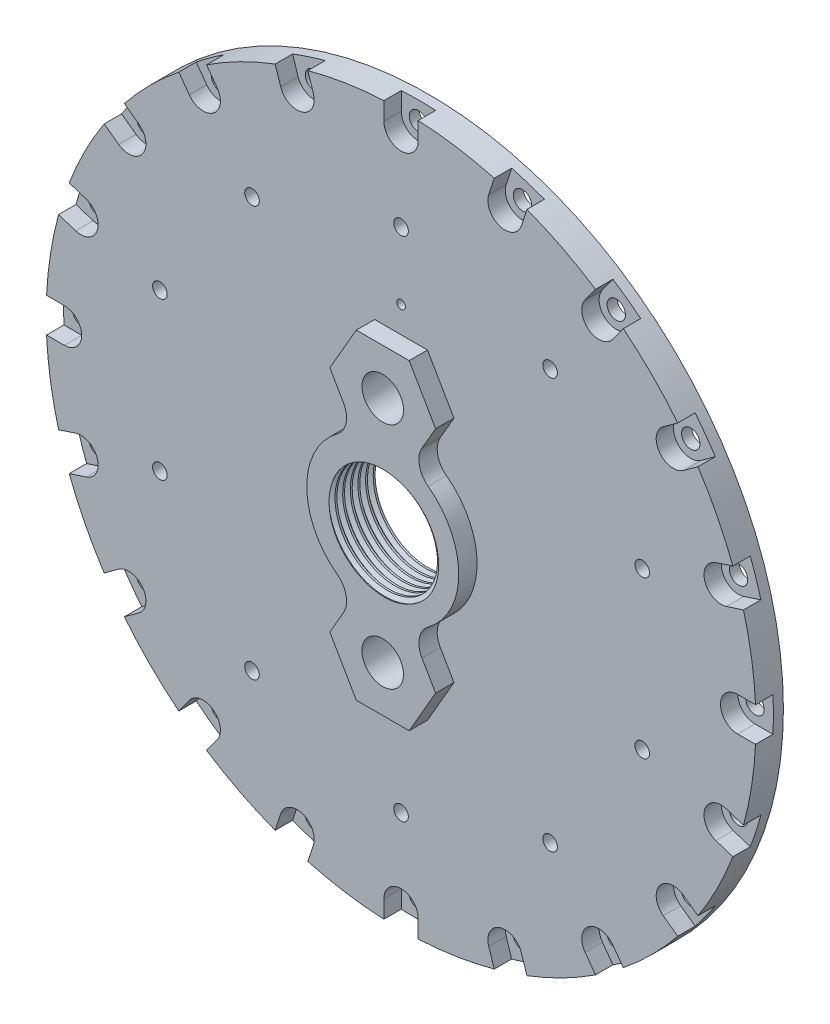
SolidWorks part; units mm, degrees
material "AISI 316 Stainless Steel Sheet (SS)"
ref_plane "Front Plane" through (0, 0, 0) normal (0, 0, 1) x (1, 0, 0)
ref_plane "Top Plane" through (0, 0, 0) normal (0, 1, 0) x (1, 0, 0)
ref_plane "Right Plane" through (0, 0, 0) normal (1, 0, 0) x (0, 0, -1)
sketch "Sketch1" plane through (0, 0, 0) normal (1, 0, 0) x (0, 0, -1)
  line L0 (0, 21.082) -> (0, 98.425)
  line L1 (0, 98.425) -> (7.62, 98.425)
  line L2 (7.62, 98.425) -> (7.62, 88.6333)
  line L3 (7.62, 83.82) -> (5.08, 83.82)
  line L4 (5.08, 83.82) -> (5.08, 56.8325)
  line L5 (5.08, 56.8325) -> (7.62, 56.8325)
  line L6 (7.62, 56.8325) -> (7.62, 53.0225)
  line L7 (7.62, 14.732) -> (-5.08, 14.732)
  line L8 (-5.08, 14.732) -> (-5.08, 21.082)
  line L9 (-5.08, 21.082) -> (0, 21.082)
  line L10 (0, 0) -> (59.2702, 0) construction
  line L12 (7.62, 49.6951) -> (6.2992, 49.6951)
  line L14 (7.62, 47.0535) -> (6.2992, 47.0535)
  line L15 (6.2992, 49.6951) -> (6.2992, 47.0535)
  line L20 (7.62, 47.0535) -> (7.62, 46.0375)
  line L21 (7.62, 85.1027) -> (7.62, 83.82)
  line L22 (7.62, 50.4825) -> (7.62, 49.6951)
  line L23 (7.62, 21.59) -> (7.62, 14.732)
  line L24 (7.62, 46.0375) -> (5.08, 46.0375)
  line L26 (7.62, 21.59) -> (5.08, 21.59)
  line L27 (5.08, 46.0375) -> (5.08, 21.59)
  line L28 (7.62, 53.0225) -> (6.35, 53.0225)
  line L32 (7.62, 50.4825) -> (6.35, 50.4825)
  line L33 (6.35, 53.0225) -> (6.35, 50.4825)
  line L35 (7.62, 88.6333) -> (5.6642, 88.6333)
  line L37 (7.62, 85.1027) -> (5.6642, 85.1027)
  line L38 (5.6642, 88.6333) -> (5.6642, 85.1027)
  point P19 (6.35, 51.7525)
  point P22 (6.2992, 48.3743)
  point P31 (5.6642, 86.868)
  dimension "D1" = 196.85
  dimension "D2" = 2.54
  dimension "D3" = 7.62
  dimension "D4" = 2.54
  dimension "D5" = 113.665
  dimension "D6" = 12.7
  dimension "D7" = 29.464
  dimension "D8" = 6.35
  dimension "D9" = 2.6416
  dimension "D10" = 96.7486
  dimension "D11" = 1.3208
  dimension "D12" = 167.64
  dimension "D13" = 92.075
  dimension "D14" = 43.18
  dimension "D15" = 1.27
  dimension "D16" = 2.54
  dimension "D17" = 103.505
  dimension "D18" = 1.9558
  dimension "D19" = 3.5306
  dimension "D20" = 173.736
revolve "Revolve1" add sketch "Sketch1" angle 360 about L10 region at (0, 54.7882, -2.7116)
thread "Thread1" pitch 2.1167 method cut profile "Thread Profile1" start angle 0, offset 4.318, length 0, pitch 2.1167, diameter 29.464
ref_plane "Plane1" through (-14.732, 0, 9.398) normal (0, -1, 0) x (-1, 0, 0)
sketch "Thread Profile1" plane through (-14.732, 0, 9.398) normal (0, -1, 0) x (-1, 0, 0)
  line L0 (0, 0) -> (0, 2.1167) construction
  line L1 (0, 0) -> (1.1457, 0.6615)
  line L2 (1.1457, 0.6615) -> (1.1457, 0.926)
  line L3 (1.1457, 0.926) -> (0, 1.5875)
  line L4 (1.1457, 0.7937) -> (0, 0.7937) construction
  line L11 (0, 0) -> (0, 1.5875)
  point P2 (0, 0)
  dimension "Pitch" = 2.1167
  dimension "Profile_Angle" = 60
  dimension "Profile_Land" = 0.2646
  dimension "Profile_Height" = 1.1457
sketch "Sketch15" plane through (0, 0, 0) normal (0, 0, 1) x (1, 0, 0)
  line L10 (0, 0) -> (104.8126, 0) construction
  line L11 (7.3323, 19.05) -> (14.6647, 31.75)
  line L12 (14.6647, 31.75) -> (7.3323, 44.45)
  line L13 (7.3323, 44.45) -> (-7.3323, 44.45)
  line L14 (-7.3323, 44.45) -> (-14.6647, 31.75)
  line L15 (-14.6647, 31.75) -> (-7.3323, 19.05)
  line L16 (-7.3323, 19.05) -> (7.3323, 19.05)
  line L17 (-7.3323, -19.05) -> (7.3323, -19.05)
  line L18 (-14.6647, -31.75) -> (-7.3323, -19.05)
  line L19 (-7.3323, -44.45) -> (-14.6647, -31.75)
  line L20 (7.3323, -44.45) -> (-7.3323, -44.45)
  line L21 (14.6647, -31.75) -> (7.3323, -44.45)
  line L22 (7.3323, -19.05) -> (14.6647, -31.75)
  circle A8 centre (0, 31.75) radius 12.7 construction
  circle A9 centre (0, -31.75) radius 12.7 construction
  dimension "D2" = 63.5
  dimension "D1" = 25.4
extrude "Boss-Extrude1" add sketch "Sketch15" along normal up to surface (5.08 mm away) up to face at (21.082, 0, 5.08)
hole_wizard "1/2-20 Tapped Hole2" positions "Sketch20" profile "Sketch17" tap size "1/2-20" standard "ANSI Inch" end condition through all
sketch "Sketch20" plane through (0, 0, 5.08) normal (0, 0, 1) x (1, 0, 0)
  point P9 (0, 31.75)
  point P16 (0, -31.75)
sketch "Sketch17" plane through (0, 31.75, 5.08) normal (1, 0, 0) x (0, -1, 0)
  line L0 (0, 0) -> (0, 13.4424)
  line L1 (0, 13.4424) -> (5.7544, 13.4424)
  line L2 (5.7544, 13.4424) -> (5.7544, 0)
  line L5 (5.7544, 0) -> (0, 0)
  line L11 (0, -6.35) -> (0, 107.95) construction
  dimension "Thru Tap Drill Dia." = 11.5087
  dimension "Thru Tap Drill Depth" = 13.4424
cosmetic thread "Hole Thread3" parameters "D2"=12.7
cosmetic thread "Hole Thread4" parameters "D2"=12.7
hole_wizard "CBORE for #10 Socket Head Cap Screw1" positions "Sketch28" profile "Sketch9" counterbore size "#10" standard "ANSI Inch" end condition up to next
sketch "Sketch28" plane through (0, 0, 0) normal (0, 0, 1) x (1, 0, 0)
  circle A0 centre (0, 0) radius 93.345 construction
  point P0 (0, 93.345)
  point P16 (28.8452, 88.7764)
  point P17 (54.8668, 75.5177)
  point P18 (75.5177, 54.8668)
  point P19 (88.7764, 28.8452)
  point P20 (93.345, 0)
  point P21 (88.7764, -28.8452)
  point P22 (75.5177, -54.8668)
  point P23 (54.8668, -75.5177)
  point P24 (28.8452, -88.7764)
  point P25 (0, -93.345)
  point P26 (-28.8452, -88.7764)
  point P27 (-54.8668, -75.5177)
  point P28 (-75.5177, -54.8668)
  point P29 (-88.7764, -28.8452)
  point P30 (-93.345, 0)
  point P31 (-88.7764, 28.8452)
  point P32 (-75.5177, 54.8668)
  point P33 (-54.8668, 75.5177)
  point P34 (-28.8452, 88.7764)
  dimension "D1" = 186.69
  dimension "D2" = 20
sketch "Sketch9" plane through (0, 93.345, 0) normal (1, 0, 0) x (0, -1, 0)
  line L0 (0, 0) -> (0, 7.62)
  line L1 (0, 7.62) -> (2.5527, 7.62)
  line L3 (2.5527, 7.62) -> (2.5527, 4.826)
  line L4 (2.5527, 4.826) -> (4.7625, 4.826)
  line L5 (4.7625, 4.826) -> (4.7625, 0)
  line L7 (4.7625, 0) -> (0, 0)
  line L11 (0, -6.35) -> (0, 107.95) construction
  dimension "Thru Hole Dia." = 5.1054
  dimension "Thru Hole Depth" = 7.62
  dimension "C'Bore Dia." = 9.525
  dimension "C'Bore Depth" = 4.826
sketch "Sketch29" plane through (0, 0, 0) normal (0, 0, 1) x (1, 0, 0)
  line L0 (4.7625, 93.345) -> (4.7625, 98.3097)
  line L1 (-4.7625, 93.345) -> (-4.7625, 98.3097)
  line L2 (33.3746, 87.3047) -> (34.9088, 92.0264)
  line L3 (24.3158, 90.2481) -> (25.85, 94.9698)
  line L4 (58.7198, 72.7184) -> (61.6379, 76.7349)
  line L5 (51.0139, 78.317) -> (53.9321, 82.3336)
  line L6 (78.317, 51.0139) -> (82.3336, 53.9321)
  line L7 (72.7184, 58.7198) -> (76.7349, 61.6379)
  line L8 (90.2481, 24.3158) -> (94.9698, 25.85)
  line L9 (87.3047, 33.3746) -> (92.0264, 34.9088)
  line L10 (93.345, -4.7625) -> (98.3097, -4.7625)
  line L11 (93.345, 4.7625) -> (98.3097, 4.7625)
  line L12 (87.3047, -33.3746) -> (92.0264, -34.9088)
  line L13 (90.2481, -24.3158) -> (94.9698, -25.85)
  line L14 (72.7184, -58.7198) -> (76.7349, -61.6379)
  line L15 (78.317, -51.0139) -> (82.3336, -53.9321)
  line L16 (51.0139, -78.317) -> (53.9321, -82.3336)
  line L17 (58.7198, -72.7184) -> (61.6379, -76.7349)
  line L18 (24.3158, -90.2481) -> (25.85, -94.9698)
  line L19 (33.3746, -87.3047) -> (34.9088, -92.0264)
  line L20 (-4.7625, -93.345) -> (-4.7625, -98.3097)
  line L21 (4.7625, -93.345) -> (4.7625, -98.3097)
  line L22 (-33.3746, -87.3047) -> (-34.9088, -92.0264)
  line L23 (-24.3158, -90.2481) -> (-25.85, -94.9698)
  line L24 (-58.7198, -72.7184) -> (-61.6379, -76.7349)
  line L25 (-51.0139, -78.317) -> (-53.9321, -82.3336)
  line L26 (-78.317, -51.0139) -> (-82.3336, -53.9321)
  line L27 (-72.7184, -58.7198) -> (-76.7349, -61.6379)
  line L28 (-90.2481, -24.3158) -> (-94.9698, -25.85)
  line L29 (-87.3047, -33.3746) -> (-92.0264, -34.9088)
  line L30 (-93.345, 4.7625) -> (-98.3097, 4.7625)
  line L31 (-93.345, -4.7625) -> (-98.3097, -4.7625)
  line L32 (-87.3047, 33.3746) -> (-92.0264, 34.9088)
  line L33 (-90.2481, 24.3158) -> (-94.9698, 25.85)
  line L34 (-72.7184, 58.7198) -> (-76.7349, 61.6379)
  line L35 (-78.317, 51.0139) -> (-82.3336, 53.9321)
  line L36 (-51.0139, 78.317) -> (-53.9321, 82.3336)
  line L37 (-58.7198, 72.7184) -> (-61.6379, 76.7349)
  line L38 (-24.3158, 90.2481) -> (-25.85, 94.9698)
  line L39 (-33.3746, 87.3047) -> (-34.9088, 92.0264)
  circle A0 centre (0, 93.345) radius 4.7625 construction
  circle A1 centre (0, 0) radius 98.425 construction
  circle A2 centre (28.8452, 88.7764) radius 4.7625
  circle A3 centre (0, 93.345) radius 4.7625
  circle A4 centre (54.8668, 75.5177) radius 4.7625
  circle A5 centre (0, 0) radius 98.425
  circle A6 centre (0, 0) radius 98.425
  circle A7 centre (75.5177, 54.8668) radius 4.7625
  circle A8 centre (88.7764, 28.8452) radius 4.7625
  circle A9 centre (93.345, 0) radius 4.7625
  circle A10 centre (88.7764, -28.8452) radius 4.7625
  circle A11 centre (75.5177, -54.8668) radius 4.7625
  circle A12 centre (54.8668, -75.5177) radius 4.7625
  circle A13 centre (28.8452, -88.7764) radius 4.7625
  circle A14 centre (0, -93.345) radius 4.7625
  circle A15 centre (-28.8452, -88.7764) radius 4.7625
  circle A16 centre (-54.8668, -75.5177) radius 4.7625
  circle A17 centre (-75.5177, -54.8668) radius 4.7625
  circle A18 centre (-88.7764, -28.8452) radius 4.7625
  circle A19 centre (-93.345, 0) radius 4.7625
  circle A20 centre (-88.7764, 28.8452) radius 4.7625
  circle A21 centre (-75.5177, 54.8668) radius 4.7625
  circle A22 centre (-54.8668, 75.5177) radius 4.7625
  circle A23 centre (-28.8452, 88.7764) radius 4.7625
  circle A25 centre (28.8452, 88.7764) radius 2.5527 construction
  point P2 (0, 0)
  point P129 (0, 0)
  circle M62 centre (0, 93.345) radius 4.7625
  circle M82 centre (0, 0) radius 98.425
  dimension "D1" = 0
  dimension "D2" = 20
extrude "Cut-Extrude1" cut sketch "Sketch29" against normal up to surface (4.826 mm away) contours L1 L0 M62 M82 region at (0, 98.2155, 0) up to face at (2.5527, 93.345, -4.826)
pattern_circular "CirPattern2" count 20 over 360 about axis through (0, 0, 0) along (0, 0, 1) of "Cut-Extrude1"
fillet "Fillet1" radius 6.35 4 edges at (-7.6711, 19.6368, 2.54) (-7.6711, -19.6368, 2.54) (7.6711, -19.6368, 2.54) (7.6711, 19.6368, 2.54)
hole_wizard "3/32 (0.09375) Dowel Hole1" positions "Sketch23" profile "Sketch22" hole size "3/32" standard "ANSI Inch" end condition up to next
sketch "Sketch23" plane through (0, 0, -6.35) normal (0, 0, -1) x (-1, 0, 0)
  line L0 (0, 50.4825) -> (0, 53.0225) construction
  circle A1 centre (0, 0) radius 50.4825 construction
  circle A2 centre (0, 0) radius 53.0225 construction
  point P0 (0, 51.7525)
  point P15 (0, 51.7525)
sketch "Sketch22" plane through (0, 51.7525, -6.35) normal (1, 0, 0) x (0, 1, 0)
  line L0 (0, 0) -> (0, 6.35)
  line L1 (0, 6.35) -> (1.1906, 6.35)
  line L2 (1.1906, 6.35) -> (1.1906, 0)
  line L5 (1.1906, 0) -> (0, 0)
  line L11 (0, -6.35) -> (0, 107.95) construction
  dimension "Thru Hole Dia." = 2.3812
  dimension "Thru Hole Depth" = 6.35
sketch "Sketch24" plane through (0, 0, 0) normal (0, 0, 1) x (1, 0, 0)
  line L0 (0, 56.8325) -> (0, 83.82) construction
  line L2 (14.6024, 92.1958) -> (0, 0) construction
  circle A0 centre (0, 0) radius 70.3263 construction
  circle A1 centre (0, 0) radius 56.8325 construction
  circle A2 centre (0, 0) radius 56.8325 construction
  circle A3 centre (0, 0) radius 83.82 construction
  arc A4 (0, 93.345) -> (28.8452, 88.7764) centre (0, 0) cw construction
  arc A6 (24.3158, 90.2481) -> (33.3746, 87.3047) centre (28.8452, 88.7764) ccw construction
  point P0 (0, 70.3263)
  point P14 (0, 70.3263)
  point P17 (0, 0)
sketch "Sketch25" plane through (0, 0, 0) normal (0, 0, 1) x (1, 0, 0)
  point P0 (0, 70.3263)
hole_wizard "#10-32 Tapped Hole1" positions "Sketch25" profile "Sketch27" tap size "#10-32" standard "ANSI Inch"
sketch "Sketch27" plane through (0, 70.3263, 0) normal (1, 0, 0) x (0, -1, 0)
  line L0 (0, 0) -> (0, 4.318)
  line L1 (0, 4.318) -> (2.0193, 3.1047)
  line L2 (2.0193, 3.1047) -> (2.0193, 0)
  line L5 (2.0193, 0) -> (0, 0)
  line L10 (0, 4.318) -> (-2.0193, 3.1047) construction
  line L11 (0, -6.35) -> (0, 107.95) construction
  dimension "Tap Drill Dia." = 4.0386
  dimension "Tap Drill Depth" = 4.318
  dimension "Drill Angle" = 118
cosmetic thread "Hole Thread5" parameters "D1"=9.652, "D2"=4.826
pattern_circular "CirPattern1" count 10 over 360 about axis through (0, 0, 0) along (0, 0, 1) of "#10-32 Tapped Hole1" reverse direction yes
cosmetic thread "Hole Thread6" parameters "D1"=9.652, "D2"=4.826
cosmetic thread "Hole Thread7" parameters "D1"=9.652, "D2"=4.826
cosmetic thread "Hole Thread8" parameters "D1"=9.652, "D2"=4.826
cosmetic thread "Hole Thread9" parameters "D1"=9.652, "D2"=4.826
cosmetic thread "Hole Thread10" parameters "D1"=9.652, "D2"=4.826
cosmetic thread "Hole Thread11" parameters "D1"=9.652, "D2"=4.826
cosmetic thread "Hole Thread12" parameters "D1"=9.652, "D2"=4.826
cosmetic thread "Hole Thread13" parameters "D1"=9.652, "D2"=4.826
cosmetic thread "Hole Thread14" parameters "D1"=9.652, "D2"=4.826
